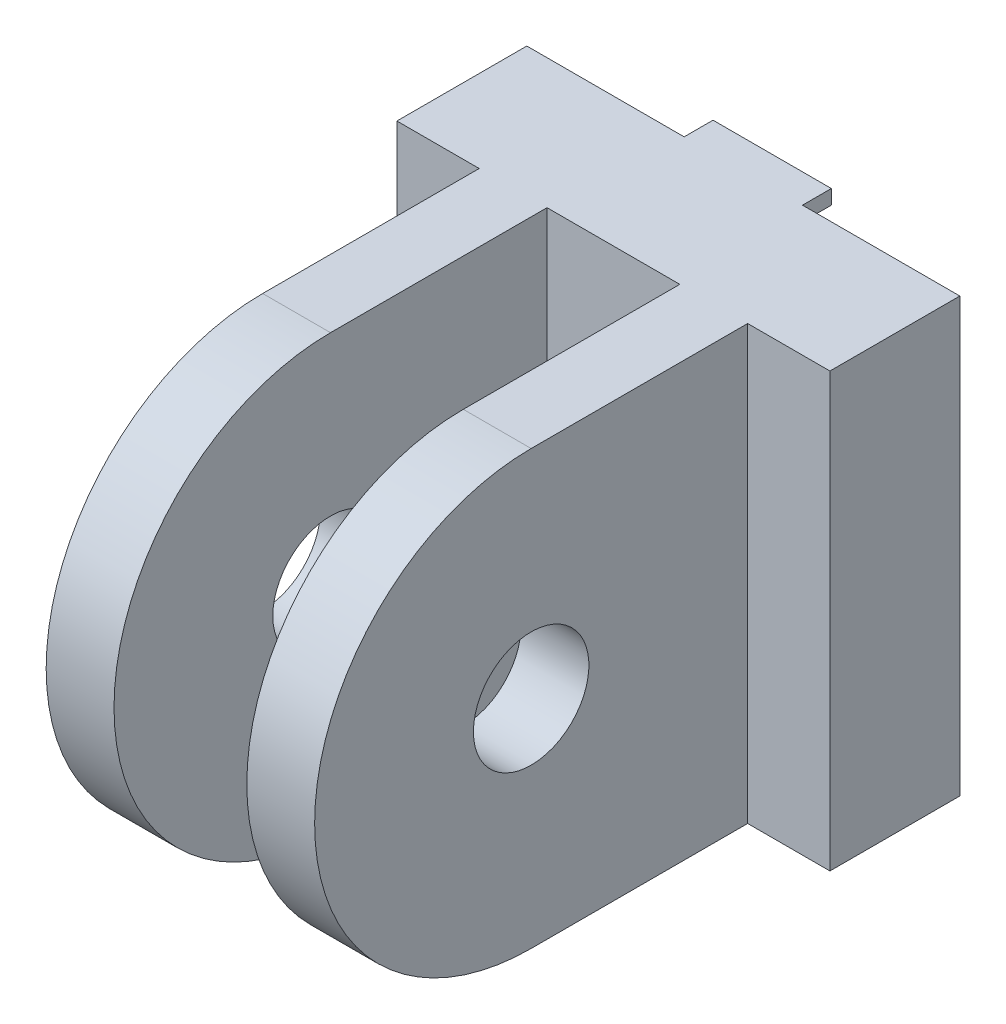
SolidWorks part; units mm, degrees
ref_plane "前视基准面" through (0, 0, 0) normal (0, 0, 1) x (1, 0, 0)
ref_plane "上视基准面" through (0, 0, 0) normal (0, 1, 0) x (1, 0, 0)
ref_plane "右视基准面" through (0, 0, 0) normal (1, 0, 0) x (0, 0, -1)
sketch "草图1" plane through (0, 0, 0) normal (0, 0, 1) x (1, 0, 0)
  line L1 (-15, -15) -> (15, -15)
  line L2 (-15, -15) -> (-15, 15)
  line L3 (-15, 15) -> (15, 15)
  line L4 (15, -15) -> (15, 15)
  line L5 (-15, -15) -> (15, 15) construction
  line L6 (-15, 15) -> (15, -15) construction
  point P0 (0, 0)
  dimension "D1" = 30
  dimension "D2" = 30
extrude "凸台-拉伸1" add sketch "草图1" along normal blind 9
sketch "草图2" plane through (0, 0, 9) normal (0, 0, 1) x (1, 0, 0)
  line L0 (15, 15) -> (-15, 15) construction
  line L1 (-9.3, -15) -> (-4.6, -15)
  line L2 (-9.3, -15) -> (-9.3, 15)
  line L3 (-9.3, 15) -> (-4.6, 15)
  line L4 (-4.6, -15) -> (-4.6, 15)
  line L5 (-9.3, -15) -> (-4.6, 15) construction
  line L6 (-9.3, 15) -> (-4.6, -15) construction
  line L7 (-15, 15) -> (-15, -15) construction
  line L8 (0, 0) -> (0, 12.1648) construction
  line L9 (9.3, -15) -> (4.6, -15)
  line L10 (9.3, -15) -> (9.3, 15)
  line L11 (4.6, -15) -> (4.6, 15)
  line L12 (9.3, 15) -> (4.6, 15)
  line L13 (-15, -15) -> (15, -15) construction
  point P0 (-6.95, 0)
  dimension "D1" = 4.7
  dimension "D2" = 5.7
extrude "凸台-拉伸2" add sketch "草图2" along normal blind 30
sketch "草图3" plane through (-9.3, 0, 0) normal (-1, 0, 0) x (0, 0, 1)
  line L0 (39, 15) -> (39, -15) construction
  line L1 (39, 15) -> (9, 15) construction
  arc A0 (24, -15) -> (24, 15) centre (24, 0) ccw
  dimension "D1" = 30
extrude "切除-拉伸2" cut sketch "草图3" against normal through all and the other way through all flip side to cut
sketch "草图4" plane through (-9.3, 0, 0) normal (-1, 0, 0) x (0, 0, 1)
  circle A0 centre (24, 0) radius 4
  dimension "D1" = 8
extrude "切除-拉伸3" cut sketch "草图4" against normal through all
sketch "草图6" plane through (0, 0, 9) normal (0, 0, 1) x (1, 0, 0)
  circle A0 centre (0, 0) radius 4
  dimension "D1" = 8
extrude "切除-拉伸5" cut sketch "草图6" against normal through all
sketch "草图7" plane through (0, 0, 0) normal (0, 0, -1) x (-1, 0, 0)
  line L0 (0, 0) -> (-17.0155, 0) construction
  line L1 (-15, 15) -> (15, 15) construction
  line L2 (-4.1, 15) -> (4.1, 15)
  line L3 (-4.1, 15) -> (-4.1, 14)
  line L4 (-4.1, 14) -> (4.1, 14)
  line L5 (4.1, 15) -> (4.1, 14)
  line L6 (4.1, -15) -> (4.1, -14)
  line L7 (-4.1, -15) -> (-4.1, -14)
  line L8 (-4.1, -14) -> (4.1, -14)
  line L9 (-4.1, -15) -> (4.1, -15)
  point P9 (0, 15)
  point P10 (0, 15)
  dimension "D1" = 1
  dimension "D2" = 8.2
extrude "凸台-拉伸3" add sketch "草图7" along normal blind 2
